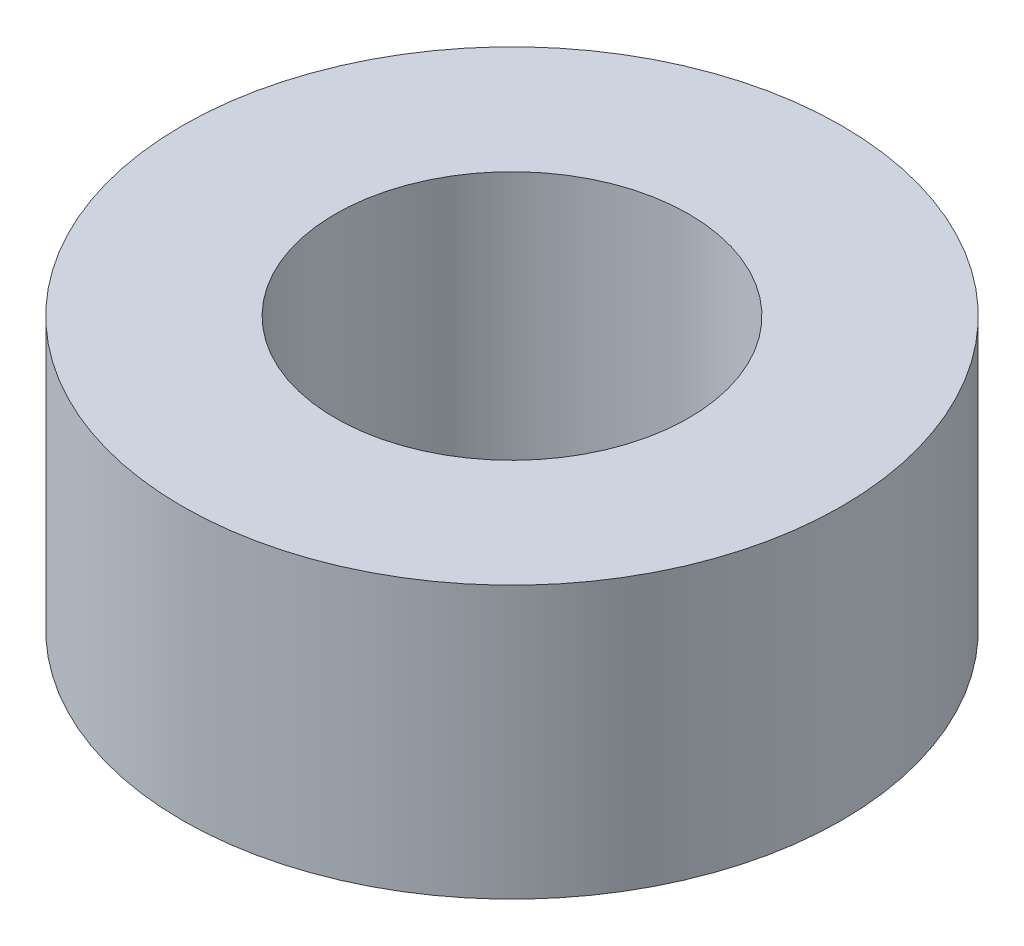
SolidWorks part; units mm, degrees
ref_plane "Piano frontale" through (0, 0, 0) normal (0, 0, 1) x (1, 0, 0)
ref_plane "Piano superiore" through (0, 0, 0) normal (0, 1, 0) x (1, 0, 0)
ref_plane "Piano destro" through (0, 0, 0) normal (1, 0, 0) x (0, 0, -1)
sketch "Schizzo1" plane through (0, 0, 0) normal (0, 0, 1) x (1, 0, 0)
  line L0 (-26, 40) -> (-48.5, 40)
  line L1 (-48.5, 40) -> (-48.5, 0)
  line L2 (-48.5, 0) -> (-26, 0)
  line L3 (-26, 0) -> (-26, 40)
  line L4 (0, 0) -> (0, 36.3355) construction
  dimension "D1" = 52
  dimension "D2" = 40
  dimension "D3" = 97
revolve "Rivoluzione1" add sketch "Schizzo1" angle 360 about L4
